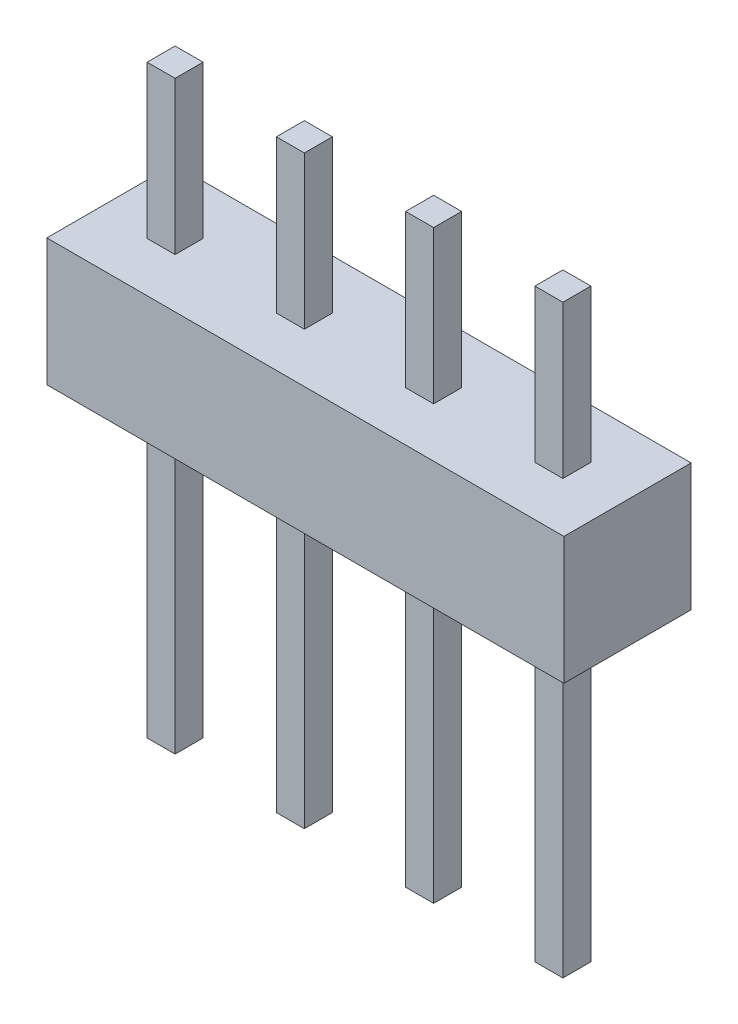
SolidWorks part; units mm, degrees
ref_plane "Front Plane" through (0, 0, 0) normal (0, 0, 1) x (1, 0, 0)
ref_plane "Top Plane" through (0, 0, 0) normal (0, 1, 0) x (1, 0, 0)
ref_plane "Right Plane" through (0, 0, 0) normal (1, 0, 0) x (0, 0, -1)
sketch "Sketch1" plane through (0, 0, 0) normal (0, 0, 1) x (1, 0, 0)
  line L1 (0, 0) -> (10.16, 0)
  line L2 (0, 0) -> (0, 2.5)
  line L3 (0, 2.5) -> (10.16, 2.5)
  line L4 (10.16, 0) -> (10.16, 2.5)
  dimension "D1" = 2.5
  dimension "D2" = 10.16
extrude "Boss-Extrude1" add sketch "Sketch1" along normal mid plane 2.5
sketch "Sketch2" plane through (0, 0, 0) normal (0, -1, 0) x (1, 0, 0)
  line L0 (0, 0) -> (10.16, 0) construction
  line L1 (10.16, 1.25) -> (10.16, -1.25) construction
  line L2 (3.535, -0.275) -> (4.085, -0.275)
  line L3 (0.995, -0.275) -> (1.545, -0.275)
  line L4 (0.995, -0.275) -> (0.995, 0.275)
  line L5 (0.995, 0.275) -> (1.545, 0.275)
  line L6 (1.545, -0.275) -> (1.545, 0.275)
  line L7 (0.995, -0.275) -> (1.545, 0.275) construction
  line L8 (0.995, 0.275) -> (1.545, -0.275) construction
  line L9 (3.535, -0.275) -> (3.535, 0.275)
  line L10 (3.535, 0.275) -> (4.085, 0.275)
  line L11 (4.085, -0.275) -> (4.085, 0.275)
  line L12 (3.535, -0.275) -> (4.085, 0.275) construction
  line L13 (3.535, 0.275) -> (4.085, -0.275) construction
  line L14 (1.27, 0) -> (3.81, 0) construction
  line L15 (6.075, -0.275) -> (6.625, -0.275)
  line L16 (6.075, -0.275) -> (6.075, 0.275)
  line L17 (6.075, 0.275) -> (6.625, 0.275)
  line L18 (6.625, -0.275) -> (6.625, 0.275)
  line L19 (6.075, -0.275) -> (6.625, 0.275) construction
  line L20 (6.075, 0.275) -> (6.625, -0.275) construction
  line L21 (8.615, -0.275) -> (9.165, -0.275)
  line L22 (8.615, -0.275) -> (8.615, 0.275)
  line L23 (8.615, 0.275) -> (9.165, 0.275)
  line L24 (9.165, -0.275) -> (9.165, 0.275)
  line L25 (8.615, -0.275) -> (9.165, 0.275) construction
  line L26 (8.615, 0.275) -> (9.165, -0.275) construction
  point P5 (1.27, 0)
  point P12 (3.81, 0)
  point P19 (6.35, 0)
  point P24 (8.89, 0)
  dimension "D1" = 0.55
  dimension "D3" = 1.27
  dimension "D4" = 2.54
  dimension "D2" = 4
extrude "Boss-Extrude2" add sketch "Sketch2" along normal blind 6 separate body
ref_axis "Axis1" through (1.27, 0, 0) along (0, -1, 0)
ref_axis "Axis2" through (8.89, 0, 0) along (0, -1, 0)
extrude "Boss-Extrude3" add sketch "Sketch2<2>" against normal blind 5.5 separate body
sketch "Sketch2<2>" plane through (0, 0, 0) normal (0, -1, 0) x (1, 0, 0) same geometry as "Sketch2"
